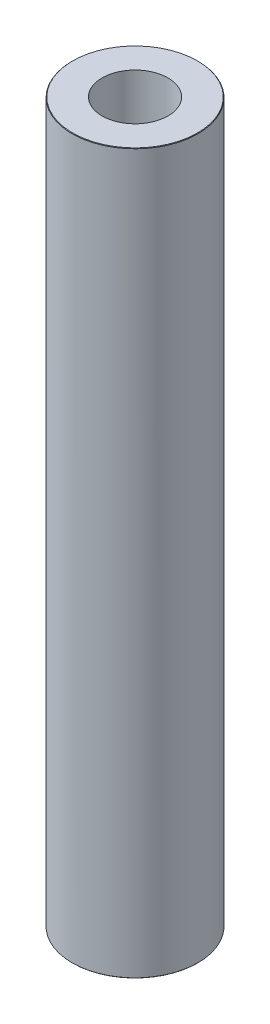
SolidWorks part; units mm, degrees
ref_plane "Front Plane" through (0, 0, 0) normal (0, 0, 1) x (1, 0, 0)
ref_plane "Top Plane" through (0, 0, 0) normal (0, 1, 0) x (1, 0, 0)
ref_plane "Right Plane" through (0, 0, 0) normal (1, 0, 0) x (0, 0, -1)
sketch "Sketch1" plane through (0, 0, 0) normal (0, 1, 0) x (1, 0, 0)
  circle A0 centre (0, 0) radius 52.5
  dimension "SHAFT_OD" = 105
extrude "Boss-Extrude1" add sketch "Sketch1" along normal blind 600
sketch "Sketch2" plane through (0, 0, 0) normal (0, 1, 0) x (1, 0, 0)
  circle A0 centre (0, 0) radius 27.5159
  dimension "BORE_D" = 55.0318
extrude "Cut-Extrude1" cut sketch "Sketch2" along normal through all
chamfer "Chamfer1" distance 0.3898 angle 45 2 edges at (0, 600, 52.5) (0, 0, 52.5)
